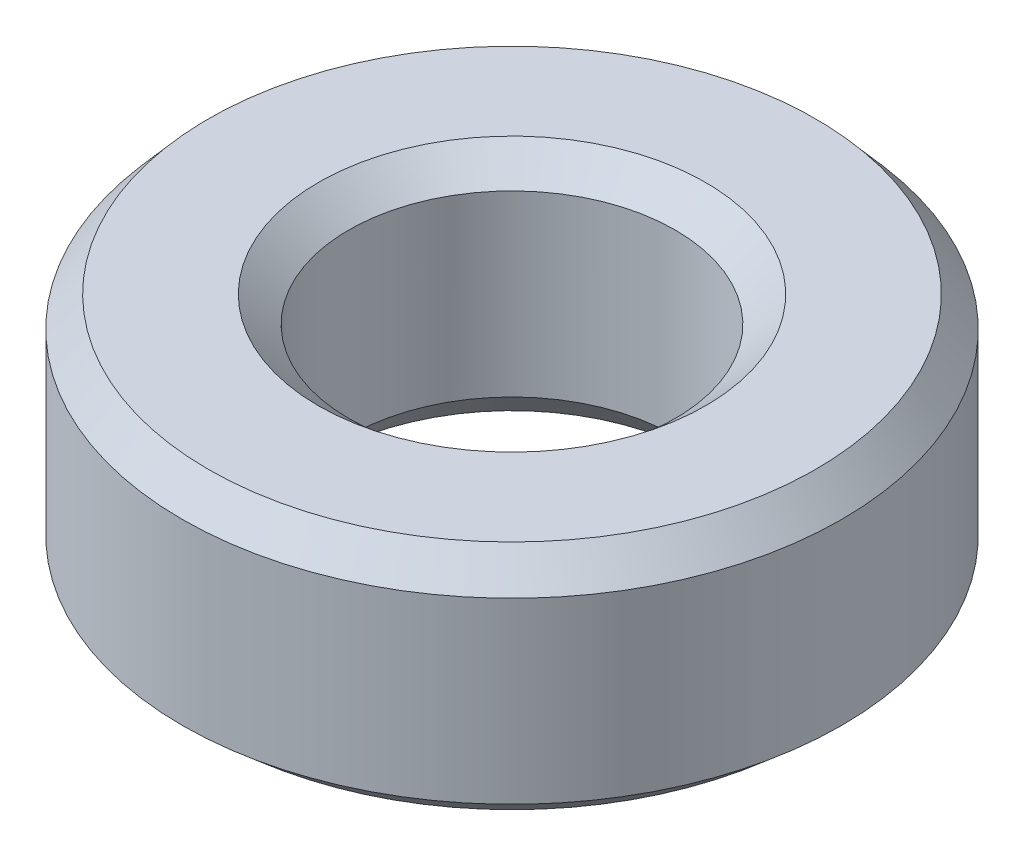
SolidWorks part; units mm, degrees
ref_plane "Front Plane" through (0, 0, 0) normal (0, 0, 1) x (1, 0, 0)
ref_plane "Top Plane" through (0, 0, 0) normal (0, 1, 0) x (1, 0, 0)
ref_plane "Right Plane" through (0, 0, 0) normal (1, 0, 0) x (0, 0, -1)
sketch "Sketch1" plane through (0, 0, 0) normal (0, 1, 0) x (1, 0, 0)
  circle A0 centre (0, 0) radius 27.5
  dimension "SLEEVE_OD" = 55
extrude "Boss-Extrude1" add sketch "Sketch1" along normal blind 19.5849
sketch "Sketch2" plane through (0, 0, 0) normal (0, 1, 0) x (1, 0, 0)
  circle A0 centre (0, 0) radius 13.6176
  dimension "BORE_D" = 27.2352
extrude "Cut-Extrude1" cut sketch "Sketch2" along normal through all
chamfer "Chamfer1" distance 2.5264 angle 40.726 4 edges at (0, 19.5849, 13.6176) (0, 0, 13.6176) (0, 0, 27.5) (0, 19.5849, 27.5) first distance on face at (0, 19.5849, 13.6176) first distance on face at (0, 0, 13.6176) first distance on face at (0, 19.5849, 27.5)
